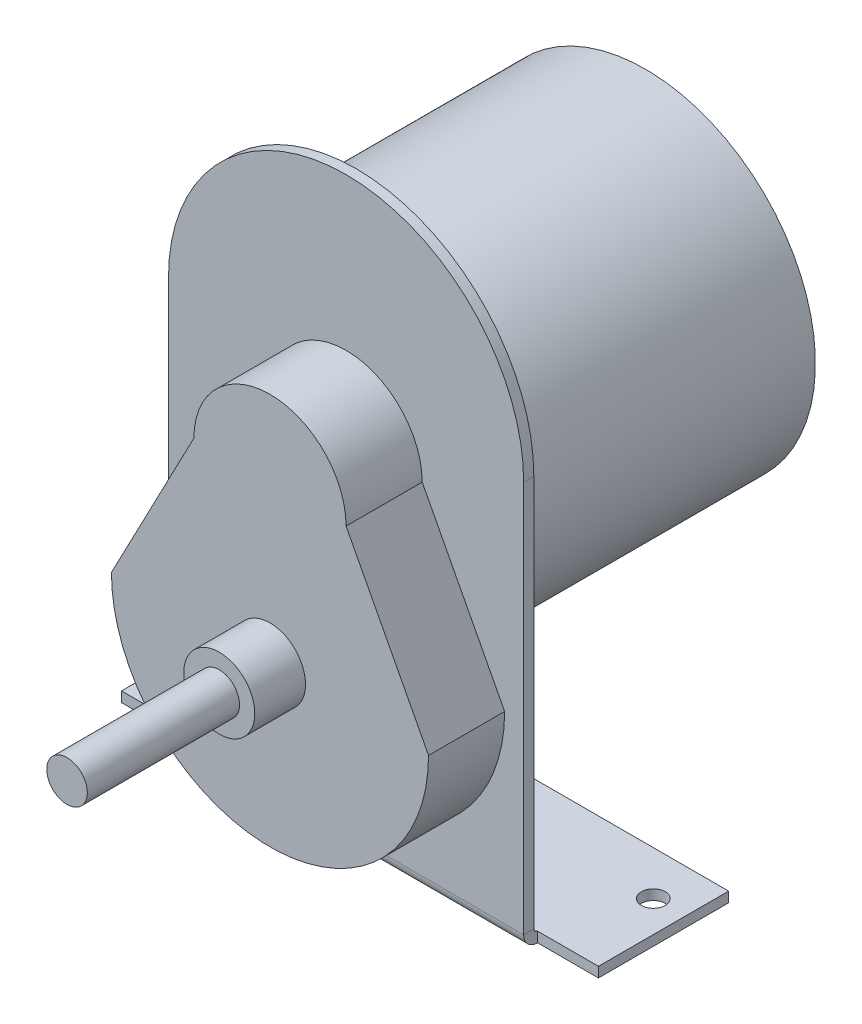
SolidWorks part; units mm, degrees
note: The reader was unsure of these and kept them because the rebuilt part matched: flange length of "Edge-Flange4".
ref_plane "Front Plane" through (0, 0, 0) normal (0, 0, 1) x (1, 0, 0)
ref_plane "Top Plane" through (0, 0, 0) normal (0, 1, 0) x (1, 0, 0)
ref_plane "Right Plane" through (0, 0, 0) normal (1, 0, 0) x (0, 0, -1)
sketch "Sketch1" plane through (0, 0, 0) normal (0, 0, 1) x (1, 0, 0)
  circle A0 centre (0, 0) radius 33.5
  dimension "D1" = 67
extrude "Boss-Extrude1" add sketch "Sketch1" along normal blind 57
sketch "Sketch2" plane through (0, 0, 57) normal (0, 0, 1) x (1, 0, 0)
  line L0 (-35, 10) -> (-35, -70)
  line L1 (-35, -70) -> (35, -70)
  line L2 (35, -70) -> (35, 10)
  line L3 (0, 0) -> (35, 0) construction
  line L4 (0, 0) -> (-35, 0) construction
  arc A0 (35, 10) -> (-35, 10) centre (0, 10) ccw
  circle A3 centre (0, 0) radius 33.5 construction
  dimension "D1" = 70
  dimension "D4" = 10
  dimension "D2" = 70
  dimension "D3" = 80
base flange "Base-Flange1" sketch "Sketch2" thickness 2 reverse thickness direction yes parameters "D1"=0.7366
edge flange "Edge-Flange4" sketch "Sketch22" flange angle 90 flange length 28.4 flange position material inside bend radius 0.7366 thickness 2 relief rectangular parameters "D6"=10
sketch "Sketch22" plane through (0, -70, 57) normal (0, -1, 0) x (-1, 0, 0)
  line L0 (35, 0) -> (-35, 0) construction
  line L1 (47, 0) -> (-47, 0)
  line L2 (-47, 0) -> (-47, 26.4)
  line L3 (-47, 26.4) -> (47, 26.4)
  line L4 (47, 26.4) -> (47, 0)
  line L5 (35, -2) -> (35, 0) construction
  line L6 (-35, -2) -> (-35, 0) construction
  dimension "D1" = 12
  dimension "D2" = 12
bend "EdgeBend4" bend radius 0.7366 bend angle 90 parameters "D5"=1
extrude "Boss-Extrude5" add sketch "Sketch12" along normal blind 15
sketch "Sketch12" plane through (0, 0, 59) normal (0, 0, 1) x (1, 0, 0)
  line L0 (-35, -67.2634) -> (35, -67.2634) construction
  line L2 (-31.25, -31.0134) -> (-15, 0)
  line L3 (15, 0) -> (31.25, -31.0134)
  arc A0 (15, 0) -> (-15, 0) centre (0, 0) ccw
  arc A1 (-31.25, -31.0134) -> (31.25, -31.0134) centre (0, -31.0134) ccw
  dimension "D1" = 30
  dimension "D2" = 62.5
  dimension "D3" = 62.5
  dimension "D4" = 36.25
  dimension "D5" = 31.25
sketch "Sketch23" plane through (0, 0, 74) normal (0, 0, 1) x (1, 0, 0)
  circle A0 centre (0, -31.0134) radius 7
  arc A1 (-31.25, -31.0134) -> (31.25, -31.0134) centre (0, -31.0134) ccw construction
  dimension "D1" = 14
extrude "Boss-Extrude6" add sketch "Sketch23" along normal blind 10
sketch "Sketch24" plane through (0, 0, 84) normal (0, 0, 1) x (1, 0, 0)
  circle A0 centre (0, -31.0134) radius 4
  circle A1 centre (0, -31.0134) radius 7 construction
  dimension "D1" = 8
extrude "Boss-Extrude7" add sketch "Sketch24" along normal blind 30
sketch "Sketch25" plane through (0, -70, 0) normal (0, -1, 0) x (1, 0, 0)
  line L0 (47, 39.3) -> (-47, 39.3) construction
  line L1 (47, 57) -> (47, 30.6) construction
  line L2 (-47, 56.2634) -> (-47, 30.6) construction
  line L3 (-47, 30.6) -> (47, 30.6) construction
  line L4 (-40.85, 39.3) -> (-40.85, 49.7197) construction
  line L5 (-40.85, 49.7197) -> (-47, 49.7197) construction
  line L6 (40.85, 39.3) -> (40.85, 49.7197) construction
  line L7 (40.85, 49.7197) -> (47, 49.7197) construction
  line L8 (47, 30.6) -> (47, 56.2634) construction
  circle A0 centre (40.85, 39.3) radius 2.35
  circle A1 centre (-40.85, 39.3) radius 2.35
  dimension "D2" = 81.7
  dimension "D3" = 4.7
  dimension "D1" = 8.7
extrude "Cut-Extrude1" cut sketch "Sketch25" against normal blind 5
ref_point "Point1"
sketch "Bend-Lines3" [suppressed] plane through (0, 0, 0) normal (0, 1, 0) x (1, 0, 0)
sketch "Bounding-Box3" [suppressed] plane through (0, 0, 0) normal (0, 1, 0) x (1, 0, 0)
sheet metal parameters "Sheet-Metal5" thickness 2 parameters "D1"=0.7366
flat pattern "Flat-Pattern5" [suppressed]
sketch "Bend-Lines4" plane through (0, 0, 0) normal (0, 1, 0) x (1, 0, 0)
sketch3d "Bounding-Box4" [suppressed]
  line L0 (35, 35, 0) -> (35, -80, 0) construction
  line L1 (-35, 35, 0) -> (-35, -80, 0) construction
  line L2 (35, 35, 0) -> (-35, 35, 0) construction
  line L3 (35, -80, 0) -> (-35, -80, 0) construction
sheet metal parameters "Sheet-Metal7" thickness 2 parameters "D1"=0.7366
flat pattern "Flat-Pattern5"
sketch "Bend-Lines4" plane through (0, 0, 57) normal (0, 0, -1) x (-1, 0, 0)
  line L0 (-35, -68.6273) -> (35, -68.6273) construction
  line L1 (-35, -68.6273) -> (35, -68.6273) construction
sketch3d "Bounding-Box4" [suppressed]
  line L0 (-35, 35, 0) -> (-35, -99.2546, 0) construction
  line L1 (35, 35, 0) -> (35, -99.2546, 0) construction
  line L2 (-35, 35, 0) -> (35, 35, 0) construction
  line L3 (-35, -99.2546, 0) -> (35, -99.2546, 0) construction
bend of the flat pattern "Flatten-<EdgeBend4>1"
sheet metal parameters "Sheet-Metal8" thickness 2 parameters "D1"=0.7366
flat pattern "Flat-Pattern5"
sketch "Bend-Lines4" plane through (0, 0, 57) normal (0, 0, -1) x (-1, 0, 0)
  line L0 (-35, -68.6273) -> (35, -68.6273) construction
  line L1 (-35, -68.6273) -> (35, -68.6273) construction
sketch3d "Bounding-Box4" [suppressed]
  line L0 (-35, 35, 0) -> (-35, -99.2546, 0) construction
  line L1 (35, 35, 0) -> (35, -99.2546, 0) construction
  line L2 (-35, 35, 0) -> (35, 35, 0) construction
  line L3 (-35, -99.2546, 0) -> (35, -99.2546, 0) construction
bend of the flat pattern "Flatten-<EdgeBend4>1"
sheet metal parameters "Sheet-Metal9" thickness 2 parameters "D1"=0.7366
flat pattern "Flat-Pattern5"
sketch "Bend-Lines4" plane through (0, 0, 57) normal (0, 0, -1) x (-1, 0, 0)
  line L0 (-35, -68.6273) -> (35, -68.6273) construction
  line L1 (-35, -68.6273) -> (35, -68.6273) construction
sketch3d "Bounding-Box4" [suppressed]
  line L0 (-35, 35, 0) -> (-35, -99.2546, 0) construction
  line L1 (35, 35, 0) -> (35, -99.2546, 0) construction
  line L2 (-35, 35, 0) -> (35, 35, 0) construction
  line L3 (-35, -99.2546, 0) -> (35, -99.2546, 0) construction
bend of the flat pattern "Flatten-<EdgeBend4>1"
sheet metal parameters "Sheet-Metal10" thickness 2 parameters "D1"=0.7366
flat pattern "Flat-Pattern5"
sketch "Bend-Lines4" plane through (0, 0, 57) normal (0, 0, -1) x (-1, 0, 0)
  line L0 (-35, -68.6273) -> (35, -68.6273) construction
  line L1 (-35, -68.6273) -> (35, -68.6273) construction
sketch3d "Bounding-Box4" [suppressed]
  line L0 (-47, -99.2546, 0) -> (-47, 35, 0) construction
  line L1 (47, -99.2546, 0) -> (47, 35, 0) construction
  line L2 (-47, -99.2546, 0) -> (47, -99.2546, 0) construction
  line L3 (-47, 35, 0) -> (47, 35, 0) construction
bend of the flat pattern "Flatten-<EdgeBend4>1"
sheet metal parameters "Sheet-Metal11" thickness 2 parameters "D1"=0.7366
flat pattern "Flat-Pattern5"
sketch "Bend-Lines4" plane through (0, 0, 57) normal (0, 0, -1) x (-1, 0, 0)
  line L0 (-35, -68.6273) -> (35, -68.6273) construction
  line L1 (-35, -68.6273) -> (35, -68.6273) construction
sketch3d "Bounding-Box4" [suppressed]
  line L0 (-47, -105.6546, 0) -> (-47, 35, 0) construction
  line L1 (47, -105.6546, 0) -> (47, 35, 0) construction
  line L2 (-47, -105.6546, 0) -> (47, -105.6546, 0) construction
  line L3 (-47, 35, 0) -> (47, 35, 0) construction
bend of the flat pattern "Flatten-<EdgeBend4>1"
